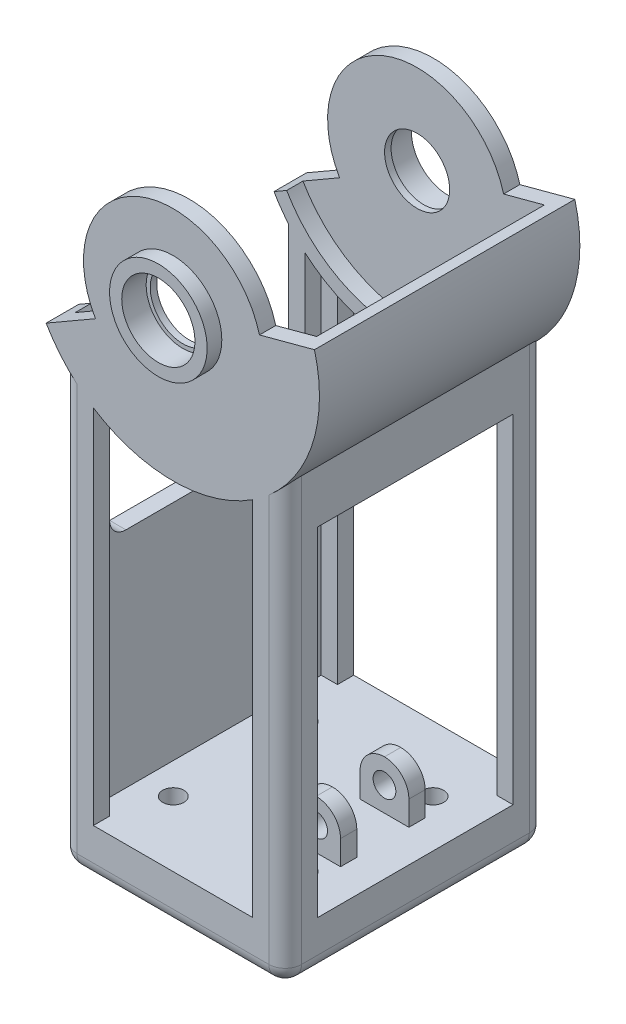
SolidWorks part; units mm, degrees
ref_plane "Front Plane" through (0, 0, 0) normal (0, 0, 1) x (1, 0, 0)
ref_plane "Top Plane" through (0, 0, 0) normal (0, 1, 0) x (1, 0, 0)
ref_plane "Right Plane" through (0, 0, 0) normal (1, 0, 0) x (0, 0, -1)
sketch "Sketch1" plane through (0, 0, 0) normal (0, 0, 1) x (1, 0, 0)
  circle A0 centre (0, 0) radius 45
  dimension "D1" = 90
extrude "Boss-Extrude1" add sketch "Sketch1" along normal blind 80
sketch "Sketch2" plane through (0, 0, 0) normal (0, 0, -1) x (-1, 0, 0)
  line L0 (0, 0) -> (0, -45) construction
  line L1 (-34.472, -28.9254) -> (34.472, -28.9254)
  line L2 (-34.472, -28.9254) -> (-34.472, -148.9254)
  line L3 (-34.472, -148.9254) -> (34.472, -148.9254)
  line L4 (34.472, -28.9254) -> (34.472, -148.9254)
  line L5 (0, 0) -> (-34.472, -28.9254) construction
  circle A0 centre (0, 0) radius 45 construction
  dimension "D1" = 120
  dimension "D2" = 50
extrude "Boss-Extrude2" add sketch "Sketch2" against normal up to surface (80 mm away) up to face at (45, 0, 80)
ref_plane "Plane1" through (0, 0, 5) normal (0, 0, -1) x (-1, 0, 0)
ref_plane "Plane2" through (0, 0, 75) normal (0, 0, 1) x (1, 0, 0)
sketch "Sketch3" plane through (0, 0, 5) normal (0, 0, -1) x (-1, 0, 0)
  circle A0 centre (0, 0) radius 40.5
  dimension "D1" = 81
extrude "Cut-Extrude1" cut sketch "Sketch3" against normal up to surface (70 mm away) up to plane "Plane2"
sketch "Sketch4" plane through (0, 0, 0) normal (0, 0, -1) x (-1, 0, 0)
  circle A0 centre (0, 0) radius 10
  dimension "D1" = 20
extrude "Cut-Extrude2" cut sketch "Sketch4" against normal up to surface (80 mm away) up to face at (0, -70.4441, 80)
sketch "Sketch5" plane through (0, 0, 0) normal (0, 0, -1) x (-1, 0, 0)
  line L0 (-26.563, 7.1175) -> (-43.4667, 11.6469)
  line L1 (0, 0) -> (0, -148.9254) construction
  line L2 (23.8157, -13.75) -> (38.9711, -22.5)
  line L3 (0, 0) -> (23.8157, -13.75) construction
  line L4 (-34.472, -148.9254) -> (34.472, -148.9254) construction
  arc A0 (23.8157, -13.75) -> (-26.563, 7.1175) centre (0, 0) ccw
  arc A1 (34.472, -28.9254) -> (-34.472, -28.9254) centre (0, 0) ccw construction
  arc A2 (38.9711, -22.5) -> (-43.4667, 11.6469) centre (0, 0) ccw
  dimension "D1" = 55
  dimension "D3" = 60
  dimension "D2" = 105
extrude "Cut-Extrude3" cut sketch "Sketch5" against normal up to surface (80 mm away) up to face at (10, 0, 80)
sketch "Sketch6" plane through (0, -148.9254, 0) normal (0, -1, 0) x (1, 0, 0)
  line L0 (34.472, 80) -> (34.472, 0) construction
  line L1 (-29.472, 75) -> (29.472, 75)
  line L2 (-29.472, 75) -> (-29.472, 5)
  line L3 (-29.472, 5) -> (29.472, 5)
  line L4 (29.472, 75) -> (29.472, 5)
  line L5 (-29.472, 75) -> (29.472, 5) construction
  line L6 (-29.472, 5) -> (29.472, 75) construction
  line L7 (34.472, 80) -> (-34.472, 80) construction
  point P0 (0, 40)
  point P9 (34.472, 40)
  dimension "D1" = 5
  dimension "D2" = 5
extrude "Cut-Extrude4" cut sketch "Sketch6" against normal up to surface (114.9195 mm away) up to face at (41.4513, -9.1895, 40)
sketch "Sketch7" plane through (0, -148.9254, 0) normal (0, -1, 0) x (1, 0, 0)
  line L0 (34.472, 80) -> (-34.472, 80) construction
  line L1 (-24.472, 80) -> (24.472, 80)
  line L2 (-24.472, 80) -> (-24.472, 75)
  line L3 (-24.472, 75) -> (24.472, 75)
  line L4 (24.472, 80) -> (24.472, 75)
  line L5 (29.472, 75) -> (-29.472, 75) construction
  line L6 (-34.472, 80) -> (-34.472, 0) construction
  line L7 (34.472, 80) -> (34.472, 0) construction
  line L8 (-34.472, 40) -> (34.472, 40) construction
  line L9 (-34.472, 80) -> (-34.472, 0) construction
  line L10 (34.472, 80) -> (34.472, 0) construction
  line L11 (-24.472, 5) -> (24.472, 5)
  line L12 (24.472, 0) -> (24.472, 5)
  line L13 (-24.472, 0) -> (24.472, 0)
  line L14 (-24.472, 0) -> (-24.472, 5)
  dimension "D1" = 10
  dimension "D2" = 10
extrude "Cut-Extrude5" cut sketch "Sketch7" against normal up to surface (111.1614 mm away) up to face at (41.4513, -9.1895, 40)
sketch "Sketch8" plane through (0, -148.9254, 0) normal (0, -1, 0) x (1, 0, 0)
  line L0 (29.472, 5) -> (29.472, 75) construction
  line L1 (29.472, 70) -> (34.472, 70)
  line L2 (29.472, 70) -> (29.472, 10)
  line L3 (29.472, 10) -> (34.472, 10)
  line L4 (34.472, 70) -> (34.472, 10)
  line L5 (34.472, 80) -> (34.472, 0) construction
  line L6 (34.472, 80) -> (24.472, 80) construction
  line L7 (34.472, 0) -> (24.472, 0) construction
  dimension "D1" = 10
  dimension "D2" = 10
ref_plane "Plane3" through (0, -45, 0) normal (0, -1, 0) x (-1, 0, 0)
extrude "Cut-Extrude6" cut sketch "Sketch8" against normal up to surface (103.9254 mm away) up to plane "Plane3"
ref_plane "Plane5" through (0, -20.25, 0) normal (0, 1, 0) x (1, 0, 0)
sketch "Sketch9" plane through (0, -20.25, 0) normal (0, 1, 0) x (1, 0, 0)
  line L0 (-38.9711, -80) -> (-38.9711, 0) construction
  line L1 (-38.9711, -10) -> (26.0289, -10)
  line L2 (-38.9711, -10) -> (-38.9711, -70)
  line L3 (-38.9711, -70) -> (26.0289, -70)
  line L4 (26.0289, -10) -> (26.0289, -70)
  line L5 (-23.8157, 0) -> (-38.9711, 0) construction
  line L6 (-23.8157, -80) -> (-38.9711, -80) construction
  dimension "D1" = 10
  dimension "D2" = 10
  dimension "D3" = 65
extrude "Cut-Extrude7" cut sketch "Sketch9" against normal blind 60
sketch "Sketch10" plane through (0, 0, 0) normal (0, 0, -1) x (-1, 0, 0)
  line L0 (0, 0) -> (0, 27.5) construction
  line L1 (0, 0) -> (96.3846, -80.8763) construction
  arc A0 (23.8157, -13.75) -> (-26.563, 7.1175) centre (0, 0) ccw construction
  dimension "D1" = 130
sketch "Sketch11" plane through (0, -148.9254, 0) normal (0, -1, 0) x (1, 0, 0)
  line L1 (-34.472, 80) -> (34.472, 80)
  line L2 (-34.472, 80) -> (-34.472, 0)
  line L3 (-34.472, 0) -> (34.472, 0)
  line L4 (34.472, 80) -> (34.472, 0)
extrude "Boss-Extrude3" add sketch "Sketch11" along normal blind 15
sketch "Sketch12" plane through (0, -148.9254, 0) normal (0, 1, 0) x (1, 0, 0)
  line L0 (-34.472, -40) -> (34.472, -40) construction
  line L1 (9.472, -27) -> (24.472, -27)
  line L2 (9.472, -27) -> (9.472, -32)
  line L3 (9.472, -32) -> (24.472, -32)
  line L4 (24.472, -27) -> (24.472, -32)
  line L5 (-34.472, -70) -> (-34.472, -10) construction
  line L6 (34.472, -10) -> (34.472, -70) construction
  line L7 (9.472, -48) -> (24.472, -48)
  line L8 (24.472, -53) -> (24.472, -48)
  line L9 (9.472, -53) -> (24.472, -53)
  line L10 (9.472, -53) -> (9.472, -48)
  dimension "D1" = 15
  dimension "D2" = 5
  dimension "D3" = 10
  dimension "D4" = 8
extrude "Boss-Extrude4" add sketch "Sketch12" along normal blind 15
fillet "Fillet1" radius 7.5 4 edges at (24.472, -133.9254, 50.5) (9.472, -133.9254, 50.5) (24.472, -133.9254, 29.5) (9.472, -133.9254, 29.5)
sketch "Sketch13" plane through (0, 0, 27) normal (0, 0, -1) x (-1, 0, 0)
  circle A0 centre (-16.972, -141.4254) radius 3.5
  dimension "D1" = 7
extrude "Cut-Extrude8" cut sketch "Sketch13" against normal up to surface (26 mm away) up to face at (16.972, -142.3041, 53)
fillet "Fillet2" radius 5 8 edges at (34.472, -163.9254, 40) (0, -163.9254, 0) (-34.472, -163.9254, 40) (0, -163.9254, 80) (34.472, -96.4254, 80) (-34.472, -96.4254, 80) (-34.472, -96.4254, 0) (34.472, -96.4254, 0)
fillet "Fillet3" radius 5 4 edges at (-31.972, -80.25, 70) (-31.972, -80.25, 10) (26.0289, -33.8682, 10) (26.0289, -33.8682, 70)
sketch "Sketch15" plane through (0, 0, 0) normal (0, 0, -1) x (-1, 0, 0)
  circle A0 centre (0, 0) radius 15
  dimension "D1" = 30
extrude "Boss-Extrude5" add sketch "Sketch15" along normal blind 4.5
ref_plane "Plane6" through (0, 0, 40) normal (0, 0, 1) x (1, 0, 0)
mirror "Mirror1" about plane through (0, 0, 40) normal (0, 0, 1) of "Boss-Extrude5"
sketch "Sketch16" plane through (0, 0, -4.5) normal (0, 0, -1) x (-1, 0, 0)
  circle A0 centre (0, 0) radius 11.25
  dimension "D1" = 22.5
extrude "Cut-Extrude9" cut sketch "Sketch16" against normal blind 7.5
mirror "Mirror2" about plane through (0, 0, 40) normal (0, 0, 1) of "Cut-Extrude9"
sketch "Sketch17" plane through (0, -163.9254, 0) normal (0, -1, 0) x (1, 0, 0)
  line L0 (55, 40) -> (-55, 40) construction
  line L1 (-25.955, 65.955) -> (25.955, 65.955) construction
  line L2 (-25.955, 65.955) -> (-25.955, 14.045) construction
  line L3 (-25.955, 14.045) -> (25.955, 14.045) construction
  line L4 (25.955, 65.955) -> (25.955, 14.045) construction
  line L5 (-25.955, 65.955) -> (25.955, 14.045) construction
  line L6 (-25.955, 14.045) -> (25.955, 65.955) construction
  line L7 (0, 65.955) -> (0, 14.045) construction
  circle A0 centre (-19.955, 59.955) radius 3.25
  circle A1 centre (19.955, 59.955) radius 3.25
  circle A2 centre (19.955, 20.045) radius 3.25
  circle A3 centre (-19.955, 20.045) radius 3.25
  point P0 (0, 40)
  dimension "D3" = 6.5
  dimension "D4" = 6
  dimension "D1" = 51.91
  dimension "D2" = 51.91
extrude "Cut-Extrude10" cut sketch "Sketch17" against normal up to surface (15 mm away) up to face at (16.972, -148.9254, 50.5)
